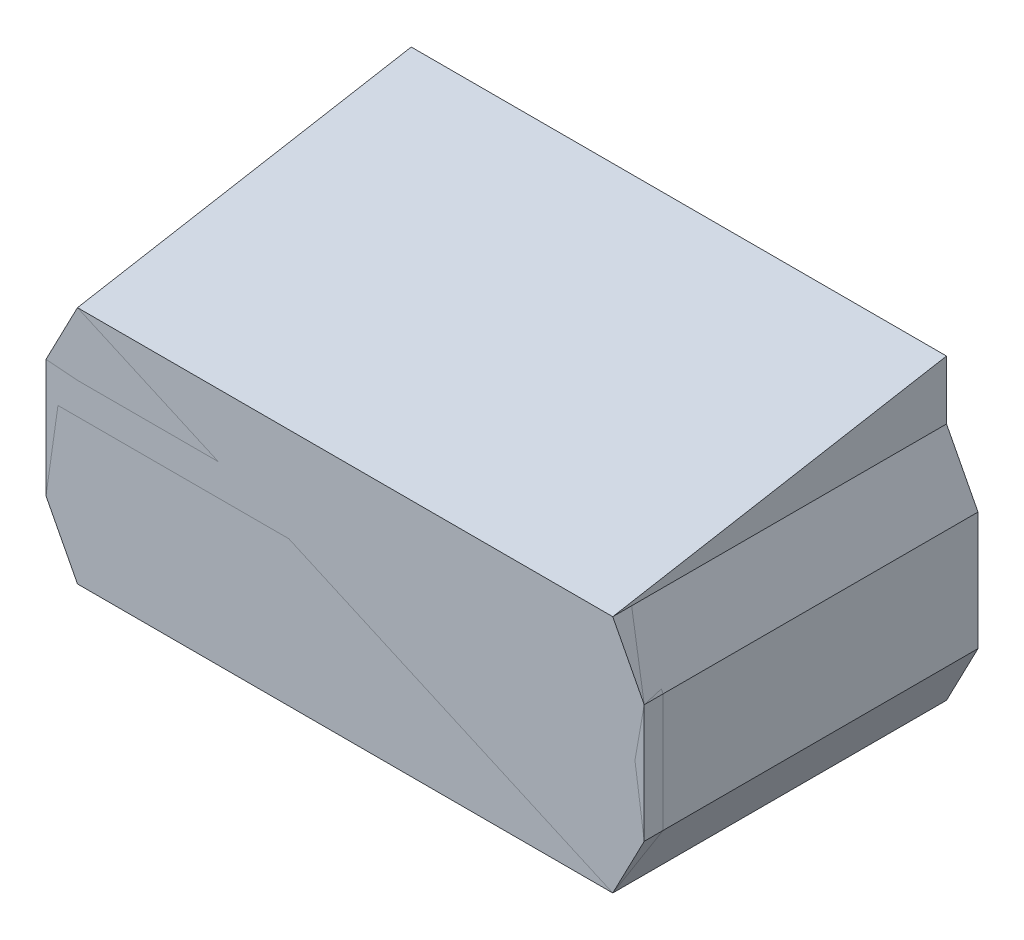
SolidWorks part; units mm, degrees
ref_plane "Front Plane" through (0, 0, 0) normal (0, 0, 1) x (1, 0, 0)
ref_plane "Top Plane" through (0, 0, 0) normal (0, 1, 0) x (1, 0, 0)
ref_plane "Right Plane" through (0, 0, 0) normal (1, 0, 0) x (0, 0, -1)
sketch "Sketch1" plane through (0, 0, 0) normal (0, 1, 0) x (1, 0, 0)
  line L1 (0, 0) -> (85, 0)
  line L2 (0, 0) -> (0, 93)
  line L3 (0, 93) -> (85, 93)
  line L4 (85, 0) -> (85, 93)
  dimension "D1" = 85
  dimension "D2" = 93
extrude "Boss-Extrude1 (Base)" add sketch "Sketch1" along normal blind 3
sketch "Sketch4" plane through (0, 0, 0) normal (0, 0, 1) x (1, 0, 0)
  line L0 (-3.1, 23) -> (0, 26.1)
  line L1 (0, 26.1) -> (0, 23)
  line L2 (0, 23) -> (-3.1, 23)
  line L3 (0, 3) -> (85, 3) construction
  line L6 (0, 3) -> (0, 0) construction
  line L7 (42.5, 28.9013) -> (42.5, -8.4397) construction
  line L8 (85, 3) -> (85, 0) construction
  line L9 (85, 23) -> (88.1, 23)
  line L10 (85, 26.1) -> (85, 23)
  line L11 (88.1, 23) -> (85, 26.1)
  dimension "D1" = 20
  dimension "D2" = 3.1
  dimension "D3" = 3.1
  dimension "D4" = 42.5
sketch "Sketch5" plane through (0, 0, 0) normal (0, 0, 1) x (1, 0, 0)
  line L6 (42.5, 3) -> (42.5, 26.9028) construction
  line L11 (-5, 28.3909) -> (0, 38)
  line L12 (0, 38) -> (0, 0)
  line L13 (0, 0) -> (-5, 9.6091)
  line L14 (-5, 9.6091) -> (-5, 28.3909)
  line L15 (90, 9.6091) -> (90, 28.3909)
  line L16 (0, 3) -> (85, 3) construction
  line L21 (85, 0) -> (90, 9.6091)
  line L22 (85, 38) -> (85, 0)
  line L23 (90, 28.3909) -> (85, 38)
  dimension "D1" = 5
  dimension "D2" = 35
extrude "Boss-Extrude4 (Side Walls)" add sketch "Sketch5" against normal through all
extrude "Cut-Extrude2 (Guide Holes)" cut sketch "Sketch4" against normal through all from offset 3
sketch "Sketch15" plane through (0, 0, 0) normal (0, 0, 1) x (1, 0, 0)
  line L0 (85, 23) -> (85, 3) construction
  line L1 (0, 23) -> (85, 23)
  line L2 (0, 23) -> (0, 3)
  line L3 (0, 3) -> (85, 3)
  line L4 (85, 23) -> (85, 3)
extrude "Boss-Extrude9 (Rear Wall)" add sketch "Sketch15" against normal blind 3
sketch "Sketch17" plane through (0, 23, 0) normal (0, 1, 0) x (1, 0, 0)
  line L1 (85, 3) -> (0, 3)
  line L2 (85, 3) -> (85, 0)
  line L3 (85, 0) -> (0, 0)
  line L4 (0, 3) -> (0, 0)
extrude "Boss-Extrude1 (Rear Wall)" add sketch "Sketch17" along normal blind 12 from offset 3
sketch "Sketch30" plane through (0, 0, 0) normal (0, 0, 1) x (1, 0, 0)
  line L1 (0, 26) -> (85, 26)
  line L2 (0, 26) -> (0, 28)
  line L3 (0, 28) -> (85, 28)
  line L4 (85, 26) -> (85, 28)
  point P5 (0.0875, 26.2835)
  point P7 (0, 26.1)
  point P9 (0, 0)
  point P10 (85, 26.1)
  point P11 (0, 0)
  point P12 (0, 26)
  dimension "D1" = 2
extrude "Cut-Extrude1 (Rear Wall)" cut sketch "Sketch30" against normal blind 10
sketch "Sketch20" plane through (0, 3, 0) normal (0, 1, 0) x (1, 0, 0)
  line L0 (85, 93) -> (0, 93) construction
  line L1 (0, 3) -> (3, 3)
  line L2 (0, 3) -> (0, 93)
  line L3 (0, 93) -> (3, 93)
  line L4 (3, 3) -> (3, 93)
  line L5 (42.5, 93) -> (42.5, 70.8429) construction
  line L6 (85, 3) -> (0, 3) construction
  line L7 (0, 3) -> (0, 0) construction
  line L8 (82, 3) -> (82, 93)
  line L9 (85, 93) -> (82, 93)
  line L10 (85, 3) -> (85, 93)
  line L11 (85, 3) -> (82, 3)
  dimension "D1" = 3
extrude "Boss-Extrude2 (Side Wall)" add sketch "Sketch20" along normal blind 10 from offset 25
chamfer "Chamfer1 (Side Wall)" distance 3 angle 45 2 edges at (82, 28, -48) (3, 28, -48)
sketch "Sketch26" plane through (0, 38, 0) normal (0, 1, 0) x (1, 0, 0)
  line L3 (0, 0) -> (0, 93)
  line L4 (0, 93) -> (0, 0) construction
  line L5 (0, 93) -> (3, 93)
  line L6 (3, 93) -> (0, 93) construction
  line L7 (3, 93) -> (3, 3)
  line L12 (3, 3) -> (82, 3)
  line L13 (82, 3) -> (82, 93)
  line L14 (82, 93) -> (85, 93)
  line L15 (85, 93) -> (85, 0)
  line L16 (85, 0) -> (0, 0)
extrude "Boss-Extrude5 (Side Wall)" add sketch "Sketch26" along normal blind 30
chamfer "Chamfer2 (Roof)" distance 30 angle 80 1 edges at (42.5, 68, 0) first distance on face at (42.5, 25.7, 0)
sketch "Sketch28" plane through (0, 36.8542, 6.4984) normal (0, 0.9848, 0.1736) x (1, 0, 0)
  line L1 (85, 101.0333) -> (0, 101.0333)
  line L2 (85, 101.0333) -> (85, 6.5986)
  line L3 (85, 6.5986) -> (0, 6.5986)
  line L4 (0, 101.0333) -> (0, 6.5986)
extrude "Boss-Extrude7 (Roof)" add sketch "Sketch28" against normal blind 3
sketch "Sketch29" plane through (90, 0, 0) normal (1, 0, 0) x (0, 0, -1)
  line L1 (93, 0) -> (98.083, 0)
  line L2 (93, 0) -> (93, 55.5979)
  line L3 (93, 55.5979) -> (98.083, 55.5979)
  line L4 (98.083, 0) -> (98.083, 55.5979)
extrude "Cut-Extrude1 (Clean up)" cut sketch "Sketch29" against normal through all
sketch "Sketch31" plane through (0, 0, 0) normal (0, -1, 0) x (1, 0, 0)
  line L0 (90, -93) -> (90, 0) construction
  line L1 (-5, -93) -> (90, -93)
  line L2 (-5, -93) -> (-5, -53)
  line L3 (-5, -53) -> (90, -53)
  line L4 (90, -93) -> (90, -53)
  line L5 (0, 0) -> (85, 0) construction
  dimension "D1" = 53
extrude "Cut-Extrude2 (Clean Up)" cut sketch "Sketch31" against normal through all
sketch "Sketch33" plane through (0, 0, 0) normal (0, 0, 1) x (1, 0, 0)
  line L7 (-5, 28.3909) -> (0, 38)
  line L8 (0, 38) -> (85, 38)
  line L9 (85, 38) -> (90, 28.3909)
  line L10 (90, 28.3909) -> (90, 9.6091)
  line L11 (90, 9.6091) -> (85, 0)
  line L12 (85, 0) -> (0, 0)
  line L13 (0, 0) -> (-5, 9.6091)
  line L14 (-5, 9.6091) -> (-5, 28.3909)
extrude "Boss-Extrude1" add sketch "Sketch33" against normal blind 3 separate body
